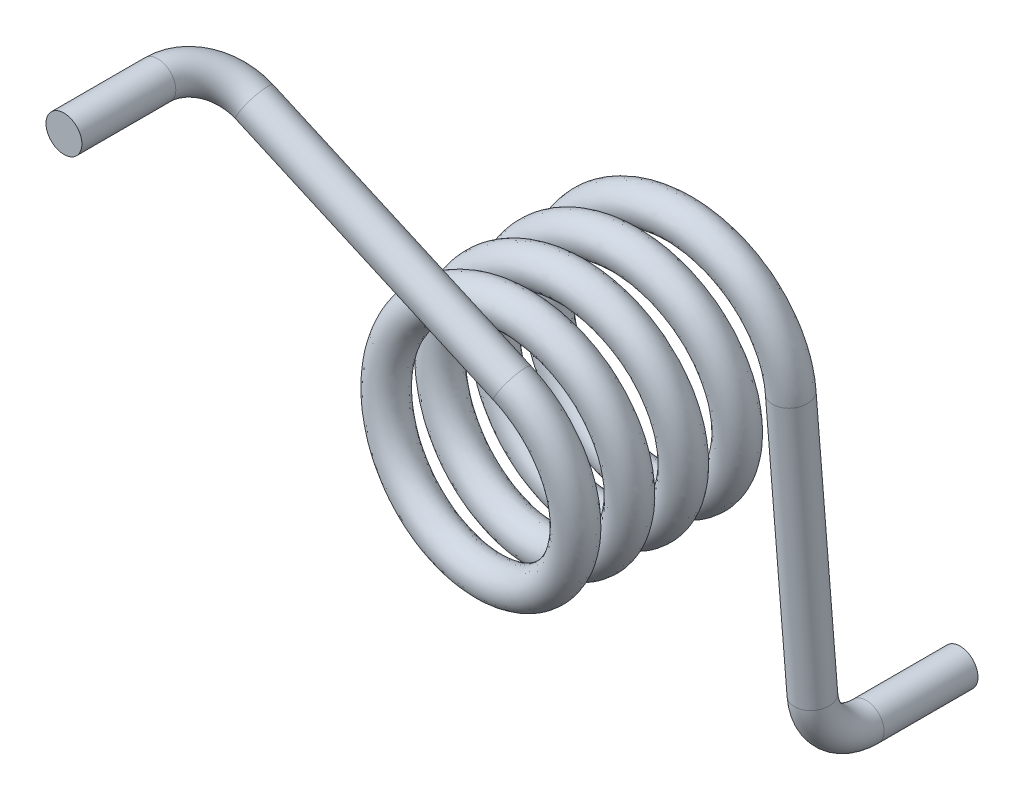
SolidWorks part; units mm, degrees
ref_plane "前视基准面" through (0, 0, 0) normal (0, 0, 1) x (1, 0, 0)
ref_plane "上视基准面" through (0, 0, 0) normal (0, 1, 0) x (1, 0, 0)
ref_plane "右视基准面" through (0, 0, 0) normal (1, 0, 0) x (0, 0, -1)
sketch "草图1" plane through (0, 0, 0) normal (0, 0, 1) x (1, 0, 0)
  circle A0 centre (0, 0) radius 6
  dimension "D1" = 12
curve "扭簧" pitch 3 height 12.5 turns 4.1667
ref_plane "基准面1" through (9, 0, 0) normal (1, 0, 0) x (0, 0, -1)
sketch "草图2" plane through (9, 0, 0) normal (1, 0, 0) x (0, 0, -1)
  line L0 (0, 0) -> (1.9448, -14.0028)
sketch "草图3" plane through (0, 0, 0) normal (0, 1, 0) x (1, 0, 0)
  line L0 (0, 0) -> (0, 30) construction
ref_plane "基准面2" through (0, 0, 0) normal (-0.5, -0.866, 0) x (-0.866, 0.5, 0)
ref_plane "基准面3" through (4.5, 7.7942, 0) normal (-0.5, -0.866, 0) x (-0.866, 0.5, 0)
sketch "草图4" plane through (4.5, 7.7942, 0) normal (-0.5, -0.866, 0) x (-0.866, 0.5, 0)
  line L0 (0, -15.8333) -> (14.0028, -17.7782)
ref_plane "基准面4" through (-7.6267, 14.7956, 17.7782) normal (-0.8578, 0.4952, 0.1376) x (0.1191, -0.0688, 0.9905)
sweep "扫描2" add path "扭簧" circular profile diameter 2 parameters "D3"=2
sketch3d "3D草图2"
  line L0 (3, 5.1962, 12.5) -> (-12.5392, 14.1679, 13.9279)
  line L1 (0, 0, 0) -> (0, 18.4611, 0) construction
  spline S0 degree 3 poles (6, 0, 0) (6, 0.7882, 0.0627) (5.6812, 2.382, 0.1896) (4.3207, 4.3892, 0.3787) (2.2892, 5.7184, 0.5682) (-0.0977, 6.1586, 0.7576) (-2.4695, 5.6427, 0.947) (-4.4578, 4.2505, 1.1364) (-5.7538, 2.1982, 1.3258) (-6.1563, -0.1954, 1.5152) (-5.6028, -2.5587, 1.7045) (-4.1792, -4.5247, 1.8939) (-2.1066, -5.788, 2.0833) (0.2931, -6.1524, 2.2727) (2.6473, -5.5615, 2.4621) (4.5904, -4.1069, 2.6515) (5.8207, -2.0145, 2.8409) (6.147, 0.3907, 3.0303) (5.5188, 2.7352, 3.2197) (4.0336, 4.655, 3.4091) (1.9219, 5.8519, 3.5985) (-0.4881, 6.14, 3.7879) (-2.8224, 5.4747, 3.9773) (-4.7184, 3.9592, 4.1667) (-5.8816, 1.8289, 4.3561) (-6.1315, -0.5855, 4.5455) (-5.4292, -2.9089, 4.7348) (-3.8838, -4.7806, 4.9242) (-1.7353, -5.9099, 5.1136) (0.6827, -6.1215, 5.303) (2.9947, -5.3824, 5.4924) (4.8416, -3.8075, 5.6818) (5.9367, -1.6413, 5.8712) (6.1099, 0.7797, 6.0606) (5.3342, 3.0797, 6.25) (3.7302, 4.9014, 6.4394) (1.5469, 5.962, 6.6288) (-0.8766, 6.0967, 6.8182) (-3.164, 5.2847, 7.0076) (-4.96, 3.652, 7.197) (-5.9858, 1.4521, 7.3864) (-6.082, -0.9732, 7.5758) (-5.2338, -3.2474, 7.7652) (-3.5728, -5.0173, 7.9545) (-1.357, -6.0081, 8.1439) (1.0696, -6.0658, 8.3333) (3.33, -5.1816, 8.5227) (5.0734, -3.4928, 8.7121) (6.0289, -1.2615, 8.9015) (6.0481, 1.1657, 9.0909) (5.1281, 3.4118, 9.2803) (3.4118, 5.1281, 9.4697) (1.1657, 6.0481, 9.6591) (-1.2615, 6.0289, 9.8485) (-3.4928, 5.0734, 10.0379) (-5.1816, 3.33, 10.2273) (-6.0658, 1.0696, 10.4167) (-6.0081, -1.357, 10.6061) (-5.0173, -3.5728, 10.7955) (-3.2474, -5.2338, 10.9848) (-0.9732, -6.082, 11.1742) (1.4521, -5.9858, 11.3636) (3.652, -4.96, 11.553) (5.2846, -3.1639, 11.7424) (6.0969, -0.8767, 11.9318) (5.9615, 1.5472, 12.1213) (4.9035, 3.729, 12.3104) (3.6826, 4.8021, 12.4373) (3, 5.1962, 12.5) knots 0 0 0 0 0.015152 0.030303 0.045455 0.060606 0.075758 0.090909 0.106061 0.121212 0.136364 0.151515 0.166667 0.181818 0.19697 0.212121 0.227273 0.242424 0.257576 0.272727 0.287879 0.30303 0.318182 0.333333 0.348485 0.363636 0.378788 0.393939 0.409091 0.424242 0.439394 0.454545 0.469697 0.484848 0.5 0.515152 0.530303 0.545455 0.560606 0.575758 0.590909 0.606061 0.621212 0.636364 0.651515 0.666667 0.681818 0.69697 0.712121 0.727273 0.742424 0.757576 0.772727 0.787879 0.80303 0.818182 0.833333 0.848485 0.863636 0.878788 0.893939 0.909091 0.924242 0.939394 0.954545 0.969697 0.984848 1 1 1 1 construction
  dimension "D1" = 18
ref_plane "基准面5" through (1.1641, 0, 12.6687) normal (-0.0915, 0, -0.9958) x (-0.8633, 0.4984, 0.0793)
ref_plane "基准面6" through (3.0001, 5.1961, 0) normal (0.5, 0.866, 0) x (-0.8633, 0.4984, 0.0793)
sketch "草图55" plane through (0, 0, 0) normal (0, 1, 0) x (1, 0, 0)
  line L0 (0, 0) -> (0, -16.1332) construction
sketch "草图54" plane through (3.0001, 5.1961, 0) normal (0.5, 0.866, 0) x (-0.8633, 0.4984, 0.0793)
  line L0 (19.2114, 15.2226) -> (19.6263, 20.4354)
  line L1 (0, 0) -> (1.2798, 16.0824) construction
  line L2 (0, 0) -> (1.2798, 16.0824) construction
  line L3 (0.9916, 12.4606) -> (18.9916, 12.4606) construction
  line L4 (0.9916, 12.4606) -> (16.2209, 12.4606)
  arc A0 (16.2209, 12.4606) -> (19.2114, 15.2226) centre (16.2209, 15.4606) ccw
  point P9 (18.9916, 12.4606)
  dimension "D1" = 3
  dimension "D2" = 8
sweep "扫描4" add path "草图54" circular profile diameter 2 parameters "D3"=2
sketch3d "3D草图3"
  line L0 (6, 0, 0) -> (6, -17.9433, -1.4279)
  circle A0 centre (6, 0, 0) radius 1 construction
  point P6 (6, 0.9968, 0.0793)
  dimension "D1" = 18
ref_plane "基准面7" through (6, 0, 0) normal (-1, 0, 0) x (0, -0.9968, -0.0793)
sketch "草图97" plane through (6, 0, 0) normal (-1, 0, 0) x (0, -0.9968, -0.0793)
  line L0 (0, 0) -> (18, 0) construction
  line L1 (0, 0) -> (15.2292, 0)
  line L2 (0, 0) -> (-1.2798, 16.0824) construction
  line L3 (0, 0) -> (-1.2798, 16.0824) construction
  line L4 (18.2198, -2.762) -> (18.6346, -7.9748)
  arc A0 (18.2198, -2.762) -> (15.2292, 0) centre (15.2292, -3) ccw
  point P7 (18, 0)
  dimension "D1" = 3
  dimension "D2" = 8
sweep "扫描5" add path "草图97" circular profile diameter 2 parameters "D3"=2
sketch "参数说明" plane through (0, 0, 0) normal (1, 0, 0) x (0, 0, -1)
  line L0 (34.9766, -5.831) -> (34.9766, -25)
  line L1 (-50.9722, 18.8612) -> (-45.7722, 18.8612)
  line L2 (36.9766, -25) -> (36.9766, 0)
  line L3 (32.2266, 8.2272) -> (10.576, 20.7272)
  line L4 (-44.7746, 17.9301) -> (-42.9447, -8.5689)
  line L5 (9.576, 18.9952) -> (31.2266, 6.4952)
  line L6 (-50.9722, 18.8612) -> (-50.9722, 20.8612)
  line L7 (-50.9722, 20.8612) -> (-45.7722, 20.8612)
  line L8 (-42.7793, 18.0679) -> (-40.9494, -8.4311)
  line L9 (-41.5482, 7.5869) -> (-41.8313, 4.3395)
  line L10 (-40.6677, -5.3395) -> (-40.9508, -8.5869)
  line L14 (-39.5543, 7.5689) -> (-38.4494, -8.4311)
  line L15 (-41.5496, 7.4311) -> (-40.4447, -8.5689)
  line L16 (-41.9471, -8.5) -> (-39.4471, -8.5) construction
  line L17 (-39.4471, -8.5) -> (-36.9471, -8.5) construction
  line L18 (-36.9471, -8.5) -> (-34.4471, -8.5) construction
  line L19 (-40.5519, 7.5) -> (-38.0519, 7.5) construction
  line L20 (-38.0519, 7.5) -> (-35.5519, 7.5) construction
  line L21 (-35.5519, 7.5) -> (-33.0519, 7.5) construction
  line L22 (-33.0519, 7.5) -> (-30.5519, 7.5) construction
  line L23 (-39.3313, 4.3395) -> (-39.0482, 7.5869)
  line L24 (-38.1677, -5.3395) -> (-38.4508, -8.5869)
  line L25 (-34.4471, -8.5) -> (-31.9471, -8.5) construction
  line L26 (-39.0496, 7.4311) -> (-37.9447, -8.5689)
  line L27 (-37.0543, 7.5689) -> (-35.9494, -8.4311)
  line L28 (-36.5496, 7.4311) -> (-35.4447, -8.5689)
  line L29 (-34.5543, 7.5689) -> (-33.4494, -8.4311)
  line L30 (-34.0496, 7.4311) -> (-32.9447, -8.5689)
  line L31 (-32.0543, 7.5689) -> (-30.9494, -8.4311)
  line L32 (8.4616, 20.7933) -> (31.7266, 7.3612) construction
  line L33 (10.576, 20.7272) -> (9.0021, 18.0012) construction
  line L34 (-34.0482, 7.5869) -> (-34.3313, 4.3395)
  line L35 (-31.5496, 7.4311) -> (-29.4339, -23.2067)
  line L36 (-36.8313, 4.3395) -> (-36.5482, 7.5869)
  line L37 (-35.6677, -5.3395) -> (-35.9508, -8.5869)
  line L38 (-31.8313, 4.3395) -> (-31.5482, 7.5869)
  line L39 (-33.1677, -5.3395) -> (-33.4508, -8.5869)
  line L40 (-26.441, -26) -> (-21.241, -26)
  line L41 (-21.241, -26) -> (-21.241, -24)
  line L42 (-21.241, -24) -> (-26.441, -24)
  line L43 (-27.4386, -23.0689) -> (-29.5543, 7.5689)
  line L44 (-30.6677, -5.3395) -> (-30.9508, -8.5869)
  line L45 (35.9766, 0) -> (35.9766, -27.1739) construction
  circle A0 centre (27.4766, 0) radius 7.5
  arc A1 (26.1768, 9.4107) -> (32.2266, 8.2272) centre (27.4766, 0) ccw
  arc A2 (34.9766, -25) -> (36.9766, -25) centre (35.9766, -25) ccw
  circle A4 centre (10.076, 19.8612) radius 1
  arc A5 (-42.9447, -8.5689) -> (-40.9494, -8.4311) centre (-41.9471, -8.5) ccw
  arc A6 (-39.5543, 7.5689) -> (-41.5496, 7.4311) centre (-40.5519, 7.5) ccw
  circle A7 centre (27.4766, 0) radius 8.5 construction
  arc A8 (-40.4447, -8.5689) -> (-38.4494, -8.4311) centre (-39.4471, -8.5) ccw
  arc A9 (-37.0543, 7.5689) -> (-39.0496, 7.4311) centre (-38.0519, 7.5) ccw
  arc A10 (-34.5543, 7.5689) -> (-36.5496, 7.4311) centre (-35.5519, 7.5) ccw
  arc A11 (-32.0543, 7.5689) -> (-34.0496, 7.4311) centre (-33.0519, 7.5) ccw
  arc A12 (-37.9447, -8.5689) -> (-35.9494, -8.4311) centre (-36.9471, -8.5) ccw
  arc A13 (-35.4447, -8.5689) -> (-33.4494, -8.4311) centre (-34.4471, -8.5) ccw
  arc A14 (-32.9447, -8.5689) -> (-30.9494, -8.4311) centre (-31.9471, -8.5) ccw
  arc A15 (-29.5543, 7.5689) -> (-31.5496, 7.4311) centre (-30.5519, 7.5) ccw
  arc A16 (-44.7746, 17.9301) -> (-45.7722, 18.8612) centre (-45.7722, 17.8612) ccw
  arc A18 (-42.7793, 18.0679) -> (-45.7722, 20.8612) centre (-45.7722, 17.8612) ccw
  arc A19 (-27.4386, -23.0689) -> (-26.441, -24) centre (-26.441, -23) ccw
  arc A21 (-29.4339, -23.2067) -> (-26.441, -26) centre (-26.441, -23) ccw
  point P54 (-42.9722, 20.8612)
  dimension "D2" = 120
  dimension "D6" = 16
  dimension "D11" = 1
  dimension "D4" = 25
  dimension "D5" = 8
  dimension "D7" = 2.5
  dimension "D9" = 2
equation "\"d\"= 2'线径（弹簧丝直径）"
equation "\"D1\"= 12'中径"
equation "\"q\"= 3'节距"
equation "\"n\"= 5'总圈数"
equation "\"θ\"= 120'展开角"
equation "\"D3@扫描2\"= \"d\"'注意：此弹簧为右旋"
equation "\"D4@扭簧\"= \"q\" '各变量含义可在设计树”参数说明”查看"
equation "\"D5@扭簧\" = \"n\" - 1 + ( ( 180 - \"θ\" ) / 360 )"
equation "\"D1@3D草图2\"= \"L\""
equation "\"D1@草图1\"=\"D1\""
equation "\"D1@3D草图3\"=\"L\""
equation "\"L\"= 18'扭转臂长度"
equation "\"J\"= 8'折弯长度"
equation "\"R\"= 2'折弯半径"
equation "\"D3@扫描4\"=\"d\""
equation "\"D3@扫描5\"=\"d\""
equation "\"D2@草图54\"=\"J\""
equation "\"D2@草图97\"=\"J\""
equation "\"D1@草图97\"=\"R\"+\"d\"/2"
equation "\"D1@草图54\"=\"R\"+\"d\"/2"
